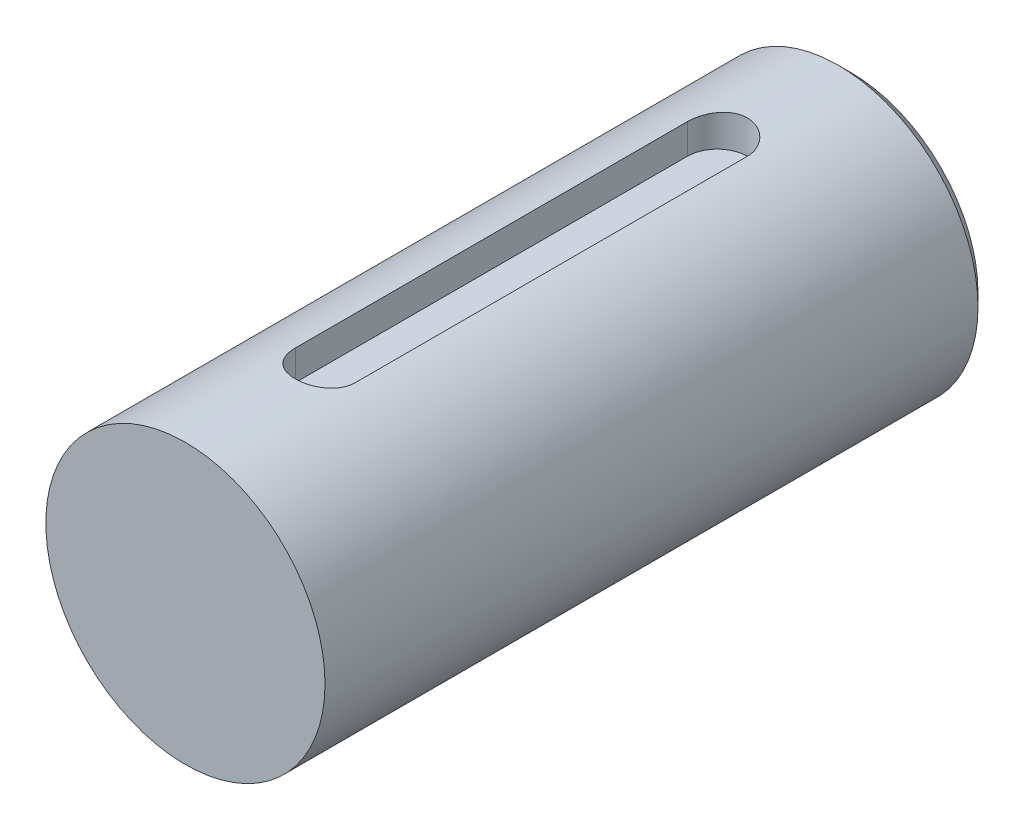
SolidWorks part; units mm, degrees
ref_plane "Płaszczyzna przednia" through (0, 0, 0) normal (0, 0, 1) x (1, 0, 0)
ref_plane "Płaszczyzna górna" through (0, 0, 0) normal (0, 1, 0) x (1, 0, 0)
ref_plane "Płaszczyzna prawa" through (0, 0, 0) normal (1, 0, 0) x (0, 0, -1)
sketch "Szkic1" plane through (0, 0, 0) normal (0, 0, 1) x (1, 0, 0)
  circle A0 centre (0, 0) radius 11.115
  dimension "D1" = 22.23
extrude "Dodanie-wyciągnięcie1" add sketch "Szkic1" along normal blind 53 contours A0
ref_plane "Płaszczyzna1" through (0, 0, 8.25) normal (0, 0, -1) x (-1, 0, 0)
chamfer "Sfazowanie1" distance 1 angle 45 1 edges at (11.115, 0, 0)
sketch "Szkic2" plane through (0, 0, 8.25) normal (0, 0, -1) x (-1, 0, 0)
  line L0 (-2.39, 10.855) -> (-2.39, 8.465)
  line L1 (-2.39, 8.465) -> (2.39, 8.465)
  line L2 (2.39, 8.465) -> (2.39, 10.855)
  circle A0 centre (0, 0) radius 11.115 construction
  arc A1 (2.39, 10.855) -> (-2.39, 10.855) centre (0, 0) ccw
  point P5 (0, 8.465)
  dimension "D1" = 4.78
  dimension "D2" = 2.39
extrude "Wytnij-wyciągnięcie1" cut sketch "Szkic2" against normal blind 36
fillet "Zaokrąglenie1" 2 edges at (-2.39, 9.66, 44.25) (2.39, 9.66, 44.25) type full round first side face at (-2.39, 9.66, 26.25) second side face at (2.39, 9.66, 26.25) middle face at (0, 9.725, 44.25)
fillet "Zaokrąglenie2" 2 edges at (-2.39, 9.66, 8.25) (2.39, 9.66, 8.25) type full round first side face at (-2.39, 9.66, 25.055) second side face at (2.39, 9.66, 25.055) middle face at (0, 9.725, 8.25)
